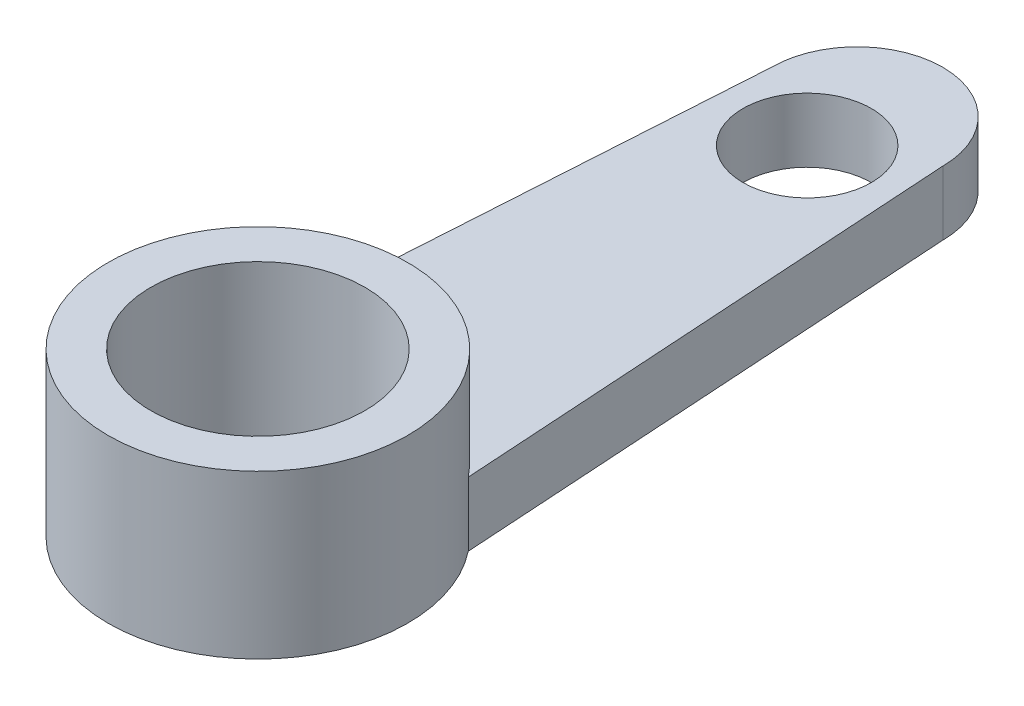
SolidWorks part; units mm, degrees
ref_plane "Front Plane" through (0, 0, 0) normal (0, 0, 1) x (1, 0, 0)
ref_plane "Top Plane" through (0, 0, 0) normal (0, 1, 0) x (1, 0, 0)
ref_plane "Right Plane" through (0, 0, 0) normal (1, 0, 0) x (0, 0, -1)
sketch "Sketch1" plane through (0, 0, 0) normal (0, 1, 0) x (1, 0, 0)
  line L0 (-27.6546, 18.9015) -> (-27.6546, -44.2727) construction
  line L1 (-27.6546, -34.378) -> (-30.4046, -34.378) construction
  line L2 (-30.4046, -34.378) -> (-30.4046, -18.378) construction
  line L4 (-30.4046, -18.378) -> (-26.398, -18.378) construction
  line L5 (-27.6546, -18.378) -> (-27.6546, -20.378) construction
  line L6 (-30.4046, -32.2129) -> (-29.6546, -20.378)
  line L7 (-24.9046, -32.2129) -> (-25.6546, -20.378)
  circle A0 centre (-27.6546, -34.378) radius 3.5
  circle A1 centre (-27.6546, -34.378) radius 2.5
  circle A2 centre (-27.6546, -20.378) radius 2
  circle A3 centre (-27.6546, -21.5452) radius 1.5
extrude "Boss-Extrude4" add sketch "Sketch1" along normal blind 1.5 contours A2 | A2 L6 A0 L7 region at (-27.6546, 0, 26.9473) region at (-27.6546, 0, 19.7206)
extrude "Boss-Extrude5" add sketch "Sketch1<7>" along normal blind 3.8 contours A0 A1 region at (-27.6546, 0, 30.9769)
sketch "Sketch1<7>" plane through (0, 0, 0) normal (0, 1, 0) x (1, 0, 0) same geometry as "Sketch1"
